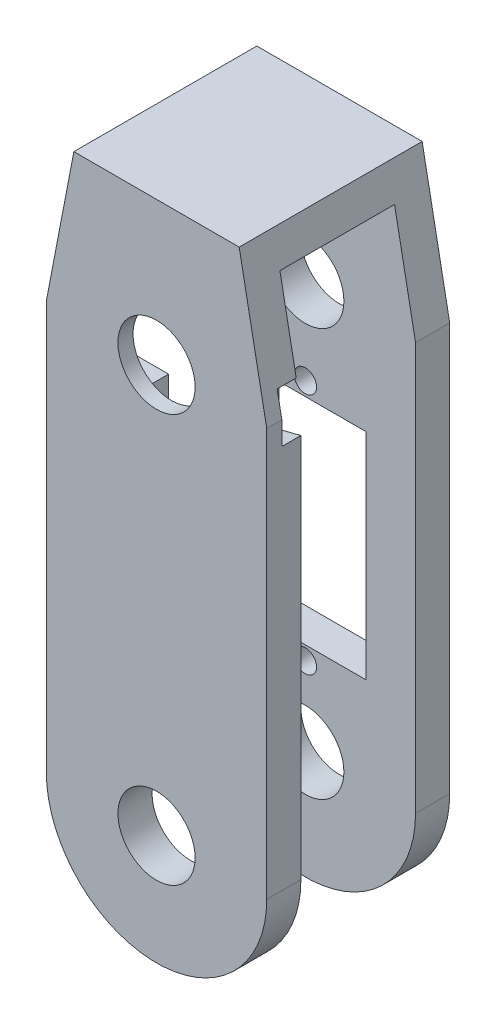
SolidWorks part; units mm, degrees
note: The reader was unsure of these and kept them because the rebuilt part matched: shared geometry of "Sketch1<5>".
ref_plane "Front Plane" through (0, 0, 0) normal (0, 0, 1) x (1, 0, 0)
ref_plane "Top Plane" through (0, 0, 0) normal (0, 1, 0) x (1, 0, 0)
ref_plane "Right Plane" through (0, 0, 0) normal (1, 0, 0) x (0, 0, -1)
sketch "Sketch1"
  line L0 (0, -11.7475) -> (0, -10.16) construction
  line L9 (-12.7, 0) -> (-9.525, 16.51)
  line L11 (12.7, -46.99) -> (12.7, 0)
  line L13 (-12.7, -46.99) -> (-12.7, 0)
  line L14 (-9.525, 16.51) -> (9.525, 16.51)
  line L15 (9.525, 16.51) -> (12.7, 0)
  line L16 (0, 16.51) -> (0, 0) construction
  line L17 (-6.985, -36.5125) -> (6.985, -36.5125)
  line L18 (-6.985, -36.5125) -> (-6.985, -11.7475)
  line L19 (-6.985, -11.7475) -> (6.985, -11.7475)
  line L20 (6.985, -36.5125) -> (6.985, -11.7475)
  line L21 (0, -38.1) -> (0, -10.16) construction
  line L22 (0, -24.13) -> (6.985, -24.13) construction
  circle A0 centre (0, 0) radius 4.445
  arc A1 (-12.7, -46.99) -> (12.7, -46.99) centre (0, -46.99) ccw
  circle A2 centre (0, -10.16) radius 1.2954
  circle A3 centre (0, -38.1) radius 1.2954
  circle A4 centre (0, -46.99) radius 4.445
  dimension "D1" = 8.89
  dimension "D5" = 76.2
  dimension "D3" = 2.5908
  dimension "D8" = 8.89
  dimension "D2" = 27.94
  dimension "D4" = 19.05
  dimension "D6" = 25.4
  dimension "D7" = 10.16
  dimension ".65" = 16.51
  dimension "D9" = 13.97
  dimension "D10" = 24.765
sketch "Sketch1<5>" plane through (0, 0, 0) normal (0, 0, 1) x (1, 0, 0) same geometry as "Sketch1"
extrude "Boss-Extrude1" add sketch "Sketch1" along normal blind 3.937
extrude "Boss-Extrude3" add sketch "Sketch1<5>" against normal blind 3.937 from offset 13.208 separate body contours L17 L20 L19 L18 | A2 | L13 A1 L11 L15 L14 L9 A4 A3 A2 L20 L17 L18 L19 A0 | A3 offset against normal yes
sketch "Sketch4" plane through (0, 0, 0) normal (0, 0, -1) x (-1, 0, 0)
  line L0 (0, 0) -> (0, 4.6245) construction
  line L1 (-13.2046, -2.54) -> (-13.2046, 2.54)
  line L2 (-2.54, -8.89) -> (2.54, -8.89)
  line L3 (-2.54, -8.89) -> (-2.54, 8.89)
  line L4 (-2.54, 8.89) -> (2.54, 8.89)
  line L5 (2.54, -8.89) -> (2.54, 8.89)
  line L6 (0, 0) -> (2.54, 0) construction
  line L7 (0, 8.89) -> (0, 0) construction
  line L8 (9.4621, 0) -> (0, 0) construction
  line L9 (13.2046, -2.54) -> (6.8783, -4.1684)
  line L10 (13.2046, 2.54) -> (6.8783, 4.1684)
  line L11 (-6.8783, -4.1684) -> (-13.2046, -2.54)
  line L12 (-13.2046, 2.54) -> (-6.8783, 4.1684)
  line L13 (-6.8783, -4.1684) -> (6.8783, -4.1684)
  line L14 (13.2046, 2.54) -> (13.2046, -2.54)
  line L15 (-6.8783, 4.1684) -> (6.8783, 4.1684)
  line L16 (-6.8783, -4.1684) -> (6.8783, 4.1684) construction
  point P17 (0, 0)
  circle M5 centre (0, 0) radius 4.445
  line M6 (12.7, -46.99) -> (12.7, 0)
  line M7 (12.7, 0) -> (9.525, 16.51)
  line M9 (-9.525, 16.51) -> (-12.7, 0)
  line M10 (-12.7, 0) -> (-12.7, -46.99)
  dimension "D1" = 17.78
  dimension "D2" = 5.08
  dimension "D3" = 5.08
extrude "Cut-Extrude4" cut sketch "Sketch4" against normal blind 2.1971 contours L15 L12 L11 L13 L3 M9 M10 M5 | L13 L3 L2 L5 M5 | L15 L5 L13 L9 L10 M5 M6 M7 | L3 L15 L5 L4 M5 | L15 L5 M5 | L15 L3 M5 | L13 L5 M5 | L3 L13 M5
sketch "Sketch5" plane through (0, 0, 0) normal (0, 0, -1) x (-1, 0, 0)
  line L0 (-9.525, 16.51) -> (9.525, 16.51)
  line L1 (9.525, 16.51) -> (10.2821, 12.573)
  line L2 (9.525, 16.51) -> (12.7, 0) construction
  line L3 (10.2821, 12.573) -> (-10.2821, 12.573)
  line L4 (-12.7, 0) -> (-9.525, 16.51) construction
  line L5 (-10.2821, 12.573) -> (-9.525, 16.51)
  dimension "D1" = 3.937
extrude "Boss-Extrude5" add sketch "Sketch5" along normal blind 16.4211
